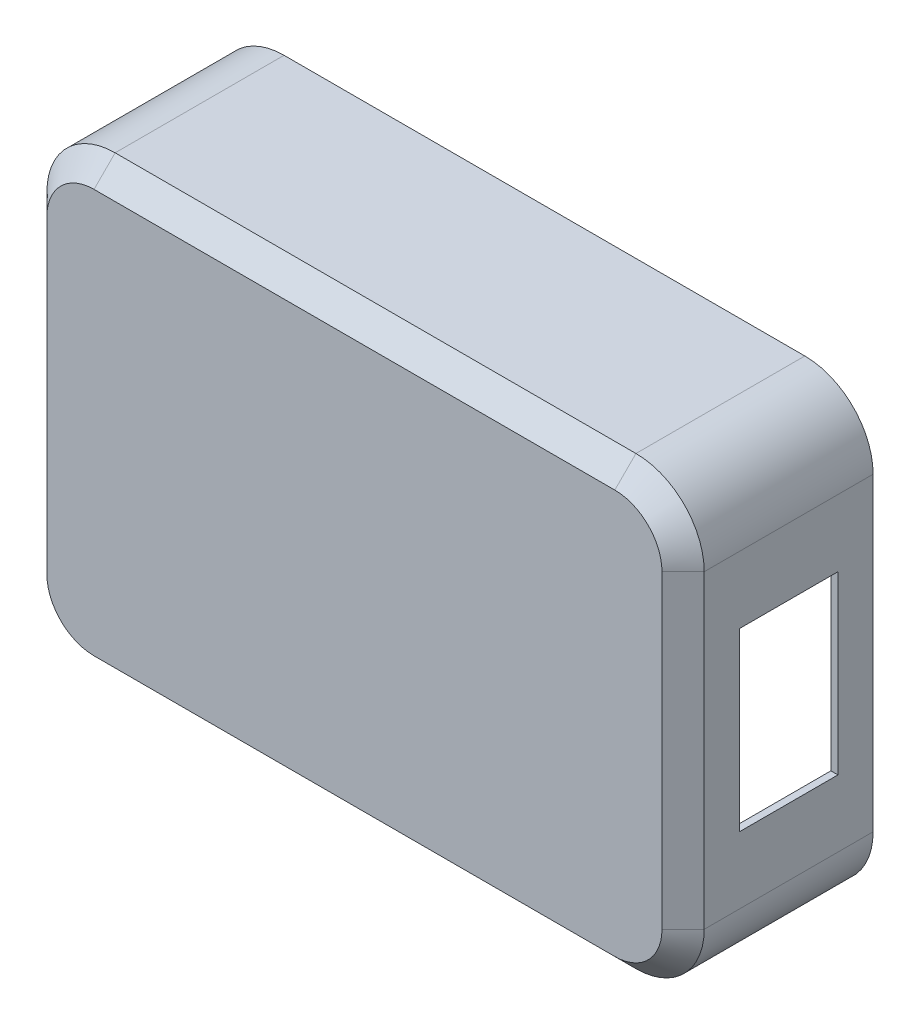
SolidWorks part; units mm, degrees
ref_plane "Front Plane" through (0, 0, 0) normal (0, 0, 1) x (1, 0, 0)
ref_plane "Top Plane" through (0, 0, 0) normal (0, 1, 0) x (1, 0, 0)
ref_plane "Right Plane" through (0, 0, 0) normal (1, 0, 0) x (0, 0, -1)
sketch "Sketch1" plane through (0, 0, 0) normal (0, 0, 1) x (1, 0, 0)
  line L22 (54.7116, -75.0987) -> (54.7116, -31.0987)
  line L23 (45.0116, -21.3987) -> (-28.9884, -21.3987)
  line L24 (-38.6884, -31.0987) -> (-38.6884, -75.0987)
  line L25 (-28.9884, -84.7987) -> (45.0116, -84.7987)
  arc A21 (54.7116, -31.0987) -> (45.0116, -21.3987) centre (45.0116, -31.0987) ccw
  arc A22 (-28.9884, -21.3987) -> (-38.6884, -31.0987) centre (-28.9884, -31.0987) ccw
  arc A23 (-38.6884, -75.0987) -> (-28.9884, -84.7987) centre (-28.9884, -75.0987) ccw
  arc A24 (45.0116, -84.7987) -> (54.7116, -75.0987) centre (45.0116, -75.0987) ccw
extrude "Boss-Extrude1" add sketch "Sketch1" along normal blind 27
chamfer "Chamfer1" distance 3 angle 45 8 edges at (8.0116, -84.7987, 27) (51.8705, -81.9576, 27) (-35.8474, -81.9576, 27) (54.7116, -53.0987, 27) (-38.6884, -53.0987, 27) (51.8705, -24.2397, 27) (-35.8474, -24.2397, 27) (8.0116, -21.3987, 27)
shell "Shell1" thickness 1 removed face at (8.0116, -53.0987, 0)
sketch "Sketch2" plane through (54.7116, 0, 0) normal (1, 0, 0) x (0, 0, -1)
  line L1 (-19, -65.5987) -> (-5, -65.5987)
  line L2 (-19, -65.5987) -> (-19, -40.5987)
  line L3 (-19, -40.5987) -> (-5, -40.5987)
  line L4 (-5, -65.5987) -> (-5, -40.5987)
  line L5 (0, -75.0987) -> (0, -31.0987) construction
  point P4 (-5, -53.0987)
  point P7 (0, -53.0987)
  dimension "D1" = 25
  dimension "D2" = 14
  dimension "D3" = 0
  dimension "D4" = 5
extrude "Cut-Extrude1" cut sketch "Sketch2" against normal up to next
sketch "Sketch3" plane through (0, 0, 0) normal (0, 0, -1) x (-1, 0, 0)
  line L0 (-54.1182, -30.9563) -> (-48.6947, -30.9563)
  line L1 (-48.6947, -30.9563) -> (-48.6947, -23.0338)
  arc A0 (-54.1182, -30.9563) -> (-48.6947, -23.0338) centre (-45.6231, -30.9541) cw
extrude "Boss-Extrude2" add sketch "Sketch3" against normal blind 4
ref_plane "Plane1" through (66.0116, -8.0987, -8) normal (0, -1, 0) x (-1, 0, 0)
sketch "Sketch7" plane through (0, 0, 0) normal (0, 0, -1) x (-1, 0, 0)
  line L0 (-53.7104, -30.9563) -> (-48.6947, -30.9563) construction
  line L1 (-48.6947, -30.9563) -> (-48.6947, -23.2168) construction
  circle A0 centre (-50.6334, -28.397) radius 1.5
  point P3 (0, 0)
  dimension "D1" = 3
  dimension "D2" = 2.5593
  dimension "D3" = 1.9387
extrude "Cut-Extrude2" cut sketch "Sketch7" against normal blind 3
ref_plane "Plane2" through (0, -53.0987, 0) normal (0, -1, 0) x (-1, 0, 0)
ref_plane "Plane3" through (8.0116, 0, 0) normal (-1, 0, 0) x (0, 0, 1)
mirror "Mirror1" about plane through (0, -53.0987, 0) normal (0, -1, 0) of "Boss-Extrude2", "Cut-Extrude2"
mirror "Mirror2" about plane through (8.0116, 0, 0) normal (-1, 0, 0) of "Mirror1"
chamfer "Chamfer2" distance 2 angle 45 4 edges at (48.6947, -75.2411, 2) (-32.6716, -75.2411, 2) (-32.6716, -30.9563, 2) (48.6947, -30.9563, 2)
chamfer "Chamfer3" distance 4 angle 45 4 edges at (-36.2894, -26.3672, 4) (-36.2894, -79.8301, 4) (52.3125, -79.8301, 4) (52.3125, -26.3672, 4)
